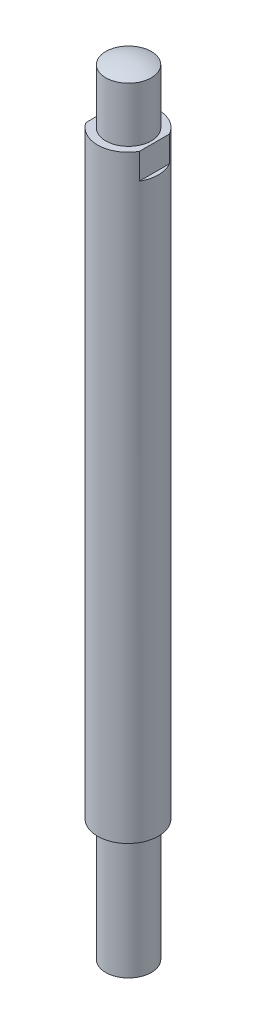
SolidWorks part; units mm, degrees
ref_plane "Front Plane" through (0, 0, 0) normal (0, 0, 1) x (1, 0, 0)
ref_plane "Top Plane" through (0, 0, 0) normal (0, 1, 0) x (1, 0, 0)
ref_plane "Right Plane" through (0, 0, 0) normal (1, 0, 0) x (0, 0, -1)
sketch "Sketch1" plane through (0, 0, 0) normal (0, 1, 0) x (1, 0, 0)
  circle A0 centre (0, 0) radius 15
  circle A1 centre (-0.3718, 0) radius 20
  dimension "D1" = 30
  dimension "D2" = 40
extrude "Boss-Extrude1" add sketch "Sketch1" along normal blind 394
extrude "Boss-Extrude2" add sketch "Sketch1<2>" along normal blind 36 from surface separate body contours A0 region at (0, 0, 0) starting at face at (-0.3718, 394, 20)
sketch "Sketch1<2>" plane through (0, 0, 0) normal (0, 1, 0) x (1, 0, 0) same geometry as "Sketch1"
extrude "Boss-Extrude3" add sketch "Sketch1<3>" against normal blind 80 from surface separate body contours A0 region at (0, 0, 0) starting at face at (-0.3718, 0, 20)
sketch "Sketch1<3>" plane through (0, 0, 0) normal (0, 1, 0) x (1, 0, 0) same geometry as "Sketch1"
sketch "Sketch2" plane through (0, 0, 0) normal (0, 1, 0) x (1, 0, 0)
  line L2 (-17, 11.1132) -> (-17, -11.1132)
  line L4 (17, 9.9106) -> (17, -9.9106)
  circle A0 centre (-0.3718, 0) radius 20 construction
  arc A1 (-17, 11.1132) -> (-17, -11.1132) centre (-0.3718, 0) ccw
  arc A2 (11.203, -16.3102) -> (17, 9.9106) centre (-0.3718, 0) ccw
  point P0 (0, 0)
extrude "Cut-Extrude1" cut sketch "Sketch2" along normal blind 17 from offset 377 contours L2 A1 | L4 A2 region at (-18.359, 0, 0) region at (18.0574, 0, 0)
dome "Dome8" faces to dome 1 distance 3 reverse direction no elliptical dome no face at (0, 430, 15) parameters "D1"=3
cosmetic thread "Cosmetic Thread1" parameters "D1"=36, "D2"=29
dome "Dome9" faces to dome 1 distance 3 reverse direction no elliptical dome no face at (0, -80, 15) parameters "D1"=3
cosmetic thread "Cosmetic Thread2" parameters "D1"=80, "D2"=29
